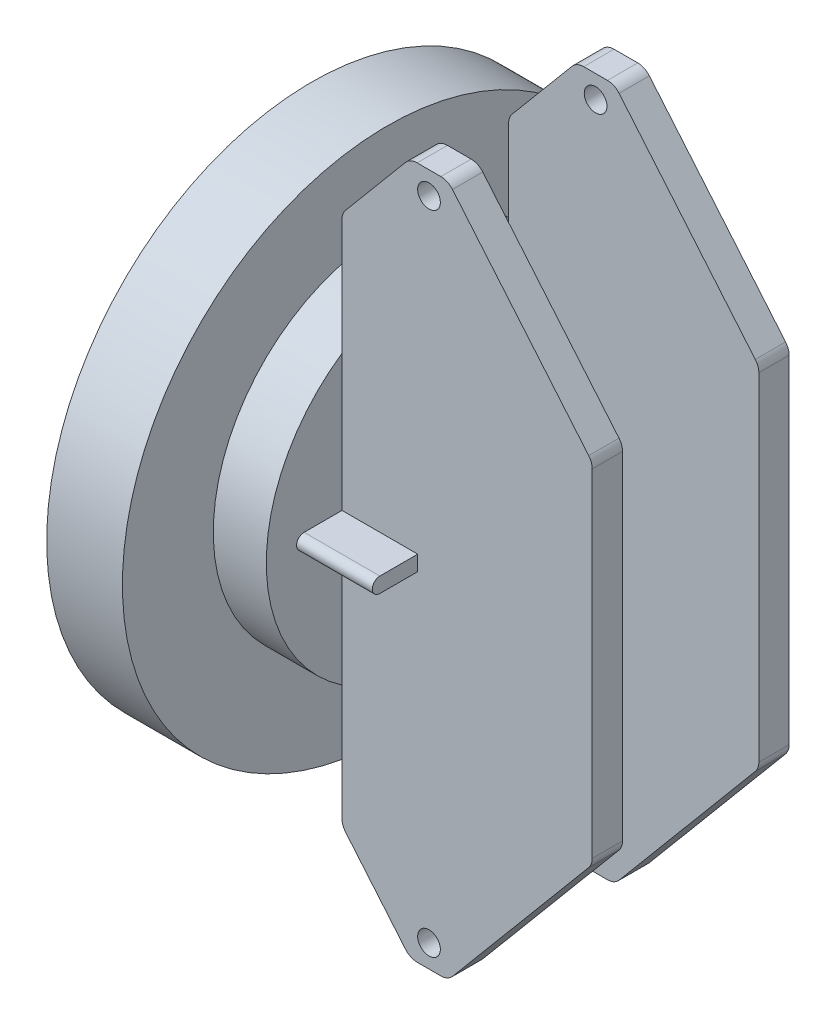
SolidWorks part; units mm, degrees
ref_plane "Front Plane" through (0, 0, 0) normal (1, 0, 0) x (0, 1, 0)
ref_plane "Top Plane" through (0, 0, 0) normal (0, 0, 1) x (0, 1, 0)
ref_plane "Right Plane" through (0, 0, 0) normal (0, 1, 0) x (-1, 0, 0)
sketch "Sketch1" plane through (0, 0, 0) normal (1, 0, 0) x (0, 1, 0)
  circle A0 centre (0, 0) radius 35
extrude "Boss-Extrude1" add sketch "Sketch1" along normal blind 10
sketch "Sketch2" plane through (10, 0, 0) normal (1, 0, 0) x (0, 1, 0)
  circle A0 centre (0, 0) radius 23
  dimension "D1" = 46
extrude "Boss-Extrude2" add sketch "Sketch2" along normal blind 7
ref_plane "Plane1" through (0, 0, 13) normal (0, 0, 1) x (0, 1, 0)
sketch "Sketch3" plane through (0, 0, 13) normal (0, 0, 1) x (0, 1, 0)
  line L0 (0, -17) -> (-51.7199, -17) construction
  line L1 (-23, -17) -> (23, -17) construction
  line L2 (0, -17) -> (0, -50.0447) construction
  line L3 (-23, -17) -> (-23, -50.0447) construction
  line L4 (-23, -10) -> (-23, -17) construction
  line L5 (35, -17) -> (-35, -17)
  line L6 (-35, -17) -> (-45.7112, -25.9878)
  line L7 (-45.7112, -25.9878) -> (-45.7112, -30.9878)
  line L8 (-45.7112, -30.9878) -> (-23, -50.0447)
  line L9 (-23, -50.0447) -> (23, -50.0447)
  line L10 (-45.7112, -14.636) -> (-45.7112, -67.2944) construction
  line L11 (45.7112, -30.9878) -> (23, -50.0447)
  line L12 (45.7112, -25.9878) -> (45.7112, -30.9878)
  line L13 (35, -17) -> (45.7112, -25.9878)
  dimension "D1" = 35
  dimension "D2" = 40
  dimension "D3" = 5
  dimension "D4" = 50
  dimension "D5" = 45.7112
extrude "Boss-Extrude3" add sketch "Sketch3" against normal blind 4
sketch "Sketch4" plane through (0, 0, 13) normal (0, 0, 1) x (1, 0, 0)
  line L0 (17, 0) -> (66.5406, 0) construction
  line L1 (17, 18.9737) -> (17, -18.9737) construction
  line L2 (25.9878, -45.7112) -> (30.9878, -45.7112) construction
  circle A0 centre (28.4878, -42.7112) radius 1.5
  circle A1 centre (28.4878, 42.7112) radius 1.5
  point P9 (28.4878, -45.7112)
  dimension "D1" = 3
extrude "Cut-Extrude2" cut sketch "Sketch4" against normal blind 4
sketch "Sketch5" plane through (17, 0, 0) normal (1, 0, 0) x (0, 1, 0)
  line L0 (18.9737, 13) -> (-18.9737, 13) construction
  line L1 (-1, 7) -> (1, 7)
  line L2 (-1, 13) -> (-1, 19)
  line L3 (-1, 19) -> (1, 19)
  line L4 (1, 13) -> (1, 19)
  line L5 (0, 13) -> (1, 19) construction
  line L6 (-1, 19) -> (0, 13) construction
  line L7 (-1, 13) -> (1, 13)
  point P0 (0, 13)
  line M5 (-18.9737, 13) -> (18.9737, 13)
extrude "Boss-Extrude4" add sketch "Sketch5" along normal blind 10 contours L4 L3 L2 M5 region at (17, 0, 16)
fillet "Fillet1" 2 edges at (22, -1, 19) (22, 1, 19) type full round first side face at (22, -1, 16) second side face at (22, 1, 16) middle face at (22, 0, 19)
fillet "Fillet2" radius 2 8 edges at (17, 35, 11) (25.9878, 45.7112, 11) (30.9878, 45.7112, 11) (50.0447, 23, 11) (50.0447, -23, 11) (30.9878, -45.7112, 11) (25.9878, -45.7112, 11) (17, -35, 11)
mirror "Mirror2" about plane through (0, 0, 0) normal (0, 0, 1) of "Fillet1", "Boss-Extrude4", "Cut-Extrude2", "Boss-Extrude3", "Fillet2"
sketch "Sketch6" plane through (0, 0, 0) normal (-1, 0, 0) x (0, -1, 0)
  circle A0 centre (0, 0) radius 15
extrude "Cut-Extrude3" cut sketch "Sketch6" against normal blind 10
ref_point "Point1"
ref_point "Point2"
ref_point "Point3"
ref_point "Point4"
ref_point "Point5"
